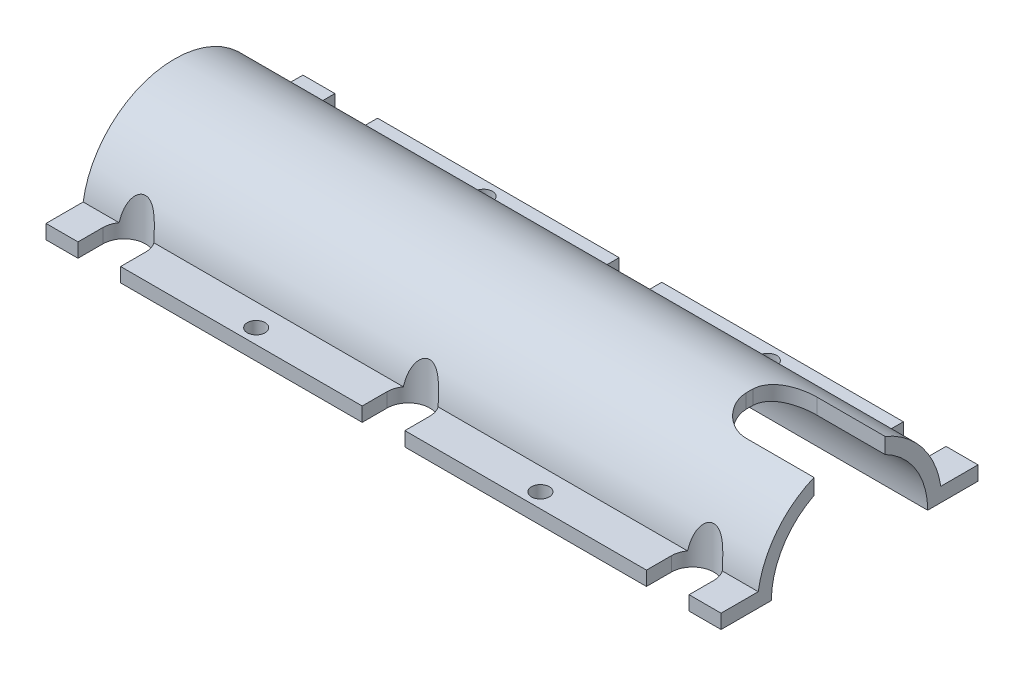
SolidWorks part; units mm, degrees
ref_plane "Спереди" through (0, 0, 0) normal (0, 0, 1) x (1, 0, 0)
ref_plane "Сверху" through (0, 0, 0) normal (0, 1, 0) x (1, 0, 0)
ref_plane "Справа" through (0, 0, 0) normal (1, 0, 0) x (0, 0, -1)
sketch "Эскиз1" plane through (0, 0, 0) normal (1, 0, 0) x (0, 0, -1)
  line L0 (11, 0) -> (18.0795, 0)
  line L1 (18.0795, 0) -> (18.0795, 2)
  line L2 (18.0795, 2) -> (12.8481, 2)
  line L3 (0, 0) -> (0, 11) construction
  line L4 (-18.0795, 2) -> (-12.848, 2.0004)
  line L5 (-18.0795, 0) -> (-18.0795, 2)
  line L6 (-11, 0) -> (-18.0795, 0)
  arc A0 (-11, 0) -> (11, 0) centre (0, 0) cw
  arc A4 (-12.848, 2.0004) -> (12.8481, 2) centre (0, 0) cw
  point P12 (-12.8452, 2)
  point P13 (0, 0)
  point P15 (0, 0)
  point P16 (12.8481, 1.9815)
extrude "Бобышка-Вытянуть1" add sketch "Эскиз1" along normal blind 95
sketch "Эскиз2" plane through (0, 2.0015, 0.0002) normal (0, 1, 0.0001) x (1, 0, 0)
  line L0 (0, -18.0793) -> (0, -14.5793) construction
  line L1 (4.5, -14.5793) -> (4.5, -18.2988)
  line L2 (0, -12.8479) -> (0, -18.0793) construction
  line L3 (0, 0) -> (95, 0) construction
  line L4 (95, -12.9061) -> (95, 12.9061) construction
  line L5 (0, -14.5793) -> (7.5, -14.5793) construction
  line L6 (4.5, -18.2988) -> (10.5, -18.2988)
  line L32 (10.5, -18.2988) -> (10.5, -14.5793)
  line L33 (50.5, -18.2988) -> (50.5, -14.5793)
  line L34 (44.5, -14.5793) -> (44.5, -18.2988)
  line L35 (44.5, -18.2988) -> (50.5, -18.2988)
  line L36 (90.5, -18.2988) -> (90.5, -14.5793)
  line L37 (84.5, -14.5793) -> (84.5, -18.2988)
  line L38 (84.5, -18.2988) -> (90.5, -18.2988)
  line L39 (84.5, 18.2988) -> (90.5, 18.2988)
  line L40 (84.5, 14.5793) -> (84.5, 18.2988)
  line L41 (90.5, 18.2988) -> (90.5, 14.5793)
  line L42 (44.5, 18.2988) -> (50.5, 18.2988)
  line L43 (44.5, 14.5793) -> (44.5, 18.2988)
  line L44 (50.5, 18.2988) -> (50.5, 14.5793)
  line L45 (4.5, 18.2988) -> (10.5, 18.2988)
  line L46 (4.5, 14.5793) -> (4.5, 18.2988)
  line L47 (10.5, 18.2988) -> (10.5, 14.5793)
  circle A0 centre (27.5, -16) radius 1.25
  circle A1 centre (67.5, -16) radius 1.25
  circle A2 centre (67.5, 16) radius 1.25
  circle A3 centre (27.5, 16) radius 1.25
  arc A10 (10.5, -14.5793) -> (4.5, -14.5793) centre (7.5, -14.5793) ccw
  arc A11 (50.5, -14.5793) -> (44.5, -14.5793) centre (47.5, -14.5793) ccw
  arc A12 (90.5, -14.5793) -> (84.5, -14.5793) centre (87.5, -14.5793) ccw
  arc A13 (90.5, 14.5793) -> (84.5, 14.5793) centre (87.5, 14.5793) cw
  arc A14 (50.5, 14.5793) -> (44.5, 14.5793) centre (47.5, 14.5793) cw
  arc A15 (10.5, 14.5793) -> (4.5, 14.5793) centre (7.5, 14.5793) cw
  dimension "D1" = 2
  dimension "D2" = 3
extrude "Вырез-Вытянуть1" cut sketch "Эскиз2" against normal through all and the other way through all
sketch "Эскиз3" plane through (0, 0, 0) normal (0, -1, 0) x (1, 0, 0)
  line L0 (0, 0) -> (95, 0) construction
  line L1 (95, -11) -> (95, 11) construction
  line L3 (85.4096, 5) -> (95, 5)
  line L4 (80.9096, 0.5) -> (80.9096, -0.5)
  line L5 (85.4096, -5) -> (95, -5)
  line L6 (95, 5) -> (95, -5)
  line L7 (80.9096, 5) -> (95, -5) construction
  line L8 (80.9096, -5) -> (95, 5) construction
  arc A0 (80.9096, 0.5) -> (85.4096, 5) centre (85.4096, 0.5) cw
  arc A1 (80.9096, -0.5) -> (85.4096, -5) centre (85.4096, -0.5) ccw
  point P5 (87.9548, 0)
  point P10 (0, 0)
  dimension "D1" = 4.5
  dimension "D2" = 4.5
extrude "Вырез-Вытянуть2" cut sketch "Эскиз3" against normal through all
